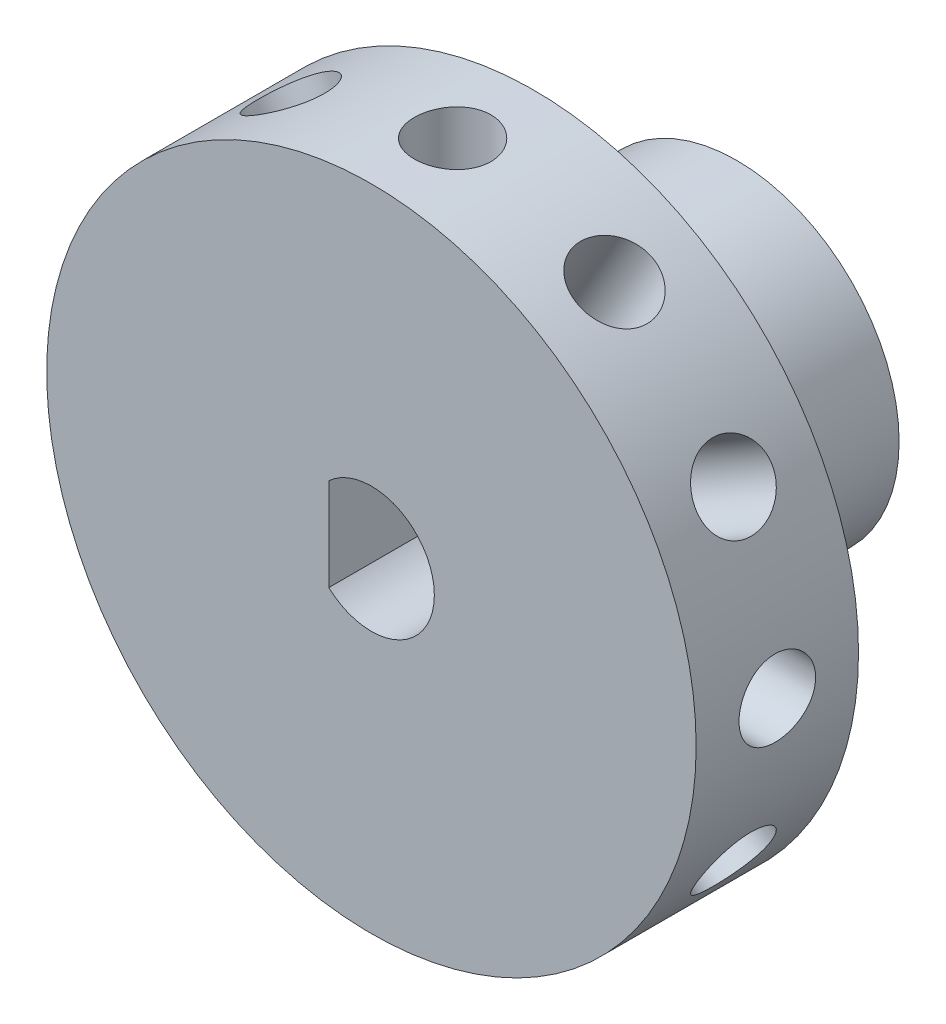
SolidWorks part; units mm, degrees
material "ABS"
ref_plane "Front Plane" through (0, 0, 0) normal (0, 0, 1) x (1, 0, 0)
ref_plane "Top Plane" through (0, 0, 0) normal (0, 1, 0) x (1, 0, 0)
ref_plane "Right Plane" through (0, 0, 0) normal (1, 0, 0) x (0, 0, -1)
ref_axis "X" through (-88.99, 0, 0) along (1, 0, 0)
ref_axis "Y" through (0, 55, 0) along (0, -1, 0)
ref_axis "Z" through (0, 0, -88.99) along (0, 0, 1)
sketch "Sketch1" plane through (0, 0, 0) normal (0, 0, 1) x (1, 0, 0)
  line L0 (-1.05, 1.1402) -> (-1.05, -1.1402)
  arc A0 (-1.05, -1.1402) -> (-1.05, 1.1402) centre (0, 0) ccw
  circle A1 centre (0, 0) radius 8
  circle A2 centre (0, 0) radius 4
  arc A3 (-1.05, 1.1402) -> (-1.05, -1.1402) centre (0, 0) ccw construction
  point P7 (-1.55, 0)
  dimension "D1" = 16
  dimension "D2" = 8
  dimension "D3" = 3.1
  dimension "D4" = 0.5
extrude "Boss-Extrude1" add sketch "Sketch1" along normal mid plane 4 contours A1 A2 | A2 A0 region at (-7.7737, 0, 0) region at (-3.8869, 0, 0)
ref_plane "Plane1" through (0, -8, 0) normal (0, -1, 0) x (-1, 0, 0)
sketch "Sketch3" plane through (0, -8, 0) normal (0, -1, 0) x (-1, 0, 0)
  circle A0 centre (0, 0) radius 0.9438
  circle A1 centre (0, 0) radius 0.7937 construction
  dimension "D1" = 0.15
extrude "Cut-Extrude1" cut sketch "Sketch3" against normal blind 4
pattern_circular "CirPattern1" count 12 over 360 about axis through (0, 0, -88.99) along (0, 0, 1) of "Cut-Extrude1"
extrude "Boss-Extrude2" add sketch "Sketch1<3>" against normal blind 5 from surface contours A2 A0 region at (-3.8869, 0, 0) starting at face at (8, 0, -2)
sketch "Sketch1<3>" plane through (0, 0, 0) normal (0, 0, 1) x (1, 0, 0) same geometry as "Sketch1"
equation "\"Axle Diameter\"= 0.4cm"
